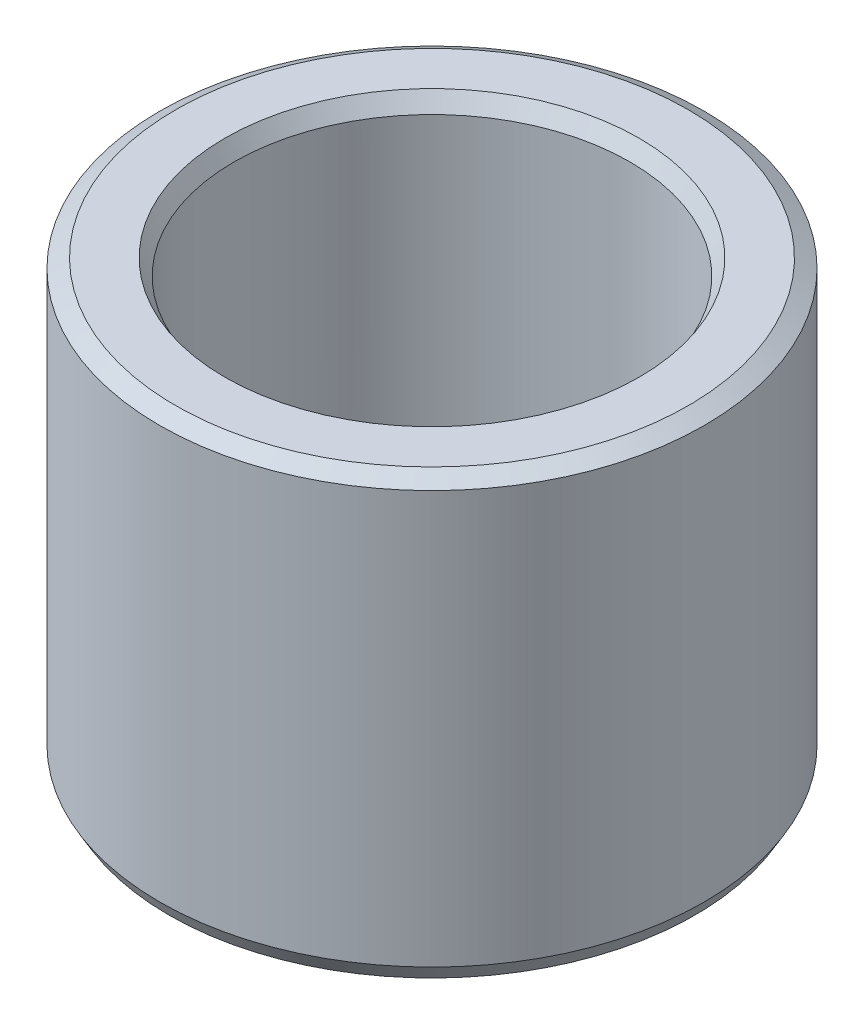
SolidWorks part; units mm, degrees
ref_plane "Front Plane" through (0, 0, 0) normal (0, 0, 1) x (1, 0, 0)
ref_plane "Top Plane" through (0, 0, 0) normal (0, 1, 0) x (1, 0, 0)
ref_plane "Right Plane" through (0, 0, 0) normal (1, 0, 0) x (0, 0, -1)
sketch "Sketch1" plane through (0, 0, 0) normal (0, 1, 0) x (1, 0, 0)
  circle A0 centre (0, 0) radius 50
  dimension "SLEEVE_OD" = 100
extrude "Boss-Extrude1" add sketch "Sketch1" along normal blind 80.4017
sketch "Sketch2" plane through (0, 0, 0) normal (0, 1, 0) x (1, 0, 0)
  circle A0 centre (0, 0) radius 36.3407
  dimension "BORE_D" = 72.6813
extrude "Cut-Extrude1" cut sketch "Sketch2" along normal through all
chamfer "Chamfer1" distance 1.6912 angle 60 4 edges at (0, 80.4017, 36.3407) (0, 0, 36.3407) (0, 0, 50) (0, 80.4017, 50) first distance on face at (0, 80.4017, 36.3407) first distance on face at (0, 0, 36.3407) first distance on face at (0, 80.4017, 50)
